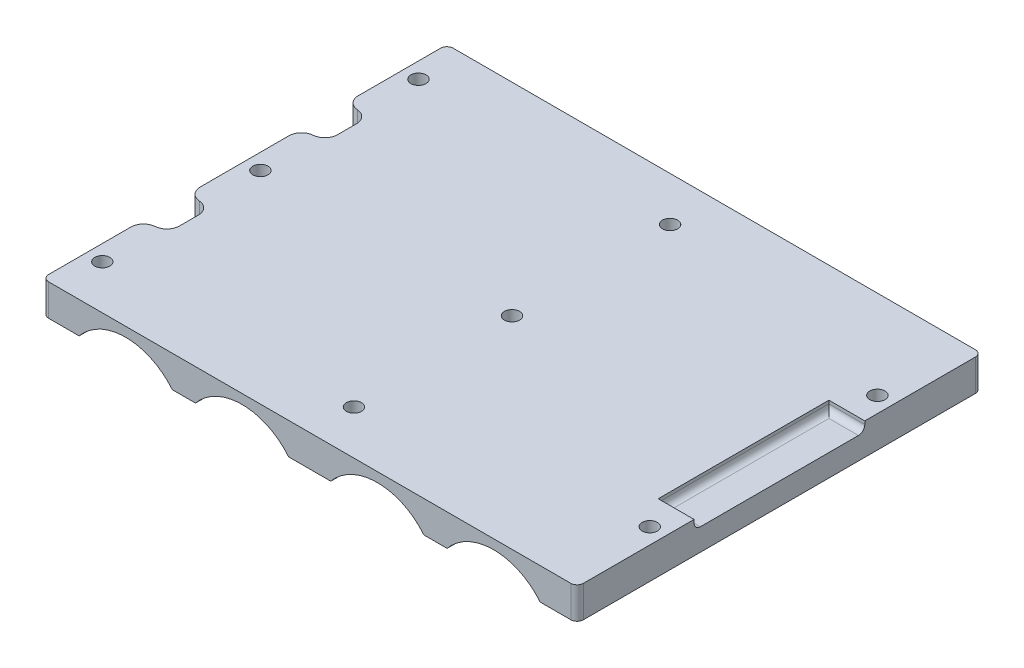
SolidWorks part; units mm, degrees
ref_plane "Front Plane" through (0, 0, 0) normal (0, 0, 1) x (1, 0, 0)
ref_plane "Top Plane" through (0, 0, 0) normal (0, 1, 0) x (1, 0, 0)
ref_plane "Right Plane" through (0, 0, 0) normal (1, 0, 0) x (0, 0, -1)
sketch "Sketch2" plane through (0, 0, 0) normal (0, 0, 1) x (1, 0, 0)
  line L2 (3.3345, -5) -> (-3.3345, -5)
  line L3 (-18.0655, -5) -> (-21.7345, -5)
  line L4 (-36.4655, -5) -> (-42.3, -5)
  line L5 (-42.3, -5) -> (-42.3, 0)
  line L7 (36.4655, -5) -> (42.3, -5)
  line L9 (18.0655, -5) -> (21.7345, -5)
  line L11 (42.3, -5) -> (42.3, 0)
  line L12 (-42.3, 0) -> (42.3, 0)
  line L13 (0, -55) -> (0, 55) construction
  line L14 (25.85, 0) -> (-25.85, 0) construction
  arc A0 (-3.3345, -5) -> (-18.0655, -5) centre (-10.7, -11) ccw
  arc A1 (-21.7345, -5) -> (-36.4655, -5) centre (-29.1, -11) ccw
  arc A2 (21.7345, -5) -> (36.4655, -5) centre (29.1, -11) cw
  arc A3 (3.3345, -5) -> (18.0655, -5) centre (10.7, -11) cw
  point P3 (0, 0)
  dimension "D1" = 9.5
  dimension "D2" = 13.2
  dimension "D3" = 11
  dimension "D4" = 18.4
  dimension "D5" = 18.4
  dimension "D6" = 5
  dimension "D7" = 21.4
extrude "Boss-Extrude1" add sketch "Sketch2" along normal mid plane 64 contours A0 L3 A1 L4 L5 L12 L11 L7 A2 L9 A3 L2
hole_wizard "M2 Clearance Hole1" positions "Sketch7" profile "Sketch8" hole size "M2" standard "ANSI Metric" end condition through all
sketch "Sketch7" plane through (0, -5, 0) normal (0, -1, 0) x (-1, 0, 0)
  line L2 (39.8, 25) -> (0, 25) construction
  line L3 (39.8, 25) -> (39.8, -25) construction
  line L4 (39.8, -25) -> (0, -25) construction
  line L5 (0, 25) -> (0, -25) construction
  line L10 (42.3, -32) -> (42.3, 32) construction
  line L12 (-42.3, -32) -> (-42.3, 32) construction
  line L13 (-36.4655, 32) -> (-42.3, 32) construction
  line L14 (-36.4655, -32) -> (-42.3, -32) construction
  line L15 (0, 55) -> (0, -55) construction
  point P0 (0, 25)
  point P2 (0, 0)
  point P4 (0, -25)
  point P6 (39.8, -25)
  point P8 (39.8, 0)
  point P10 (39.8, 25)
  point P291 (-39.8, -18)
  point P296 (-39.8, 18)
  dimension "D1" = 2.5
  dimension "D3" = 50
  dimension "D5" = 50
  dimension "D6" = 2.5
  dimension "D7" = 2.5
  dimension "D8" = 14
  dimension "D9" = 14
sketch "Sketch8" plane through (0, -5, -25) normal (1, 0, 0) x (0, 0, -1)
  line L0 (0, 0) -> (0, 5)
  line L1 (0, 5) -> (1.2, 5)
  line L2 (1.2, 5) -> (1.2, 0)
  line L5 (1.2, 0) -> (0, 0)
  line L11 (0, -6.35) -> (0, 107.95) construction
  dimension "Thru Hole Dia." = 2.4
  dimension "Thru Hole Depth" = 5
fillet "Fillet1" radius 1 4 edges at (-42.3, -2.5, -32) (42.3, -2.5, -32) (-42.3, -2.5, 32) (42.3, -2.5, 32)
sketch "Sketch9" plane through (0, 0, 0) normal (0, 1, 0) x (1, 0, 0)
  line L0 (42.3, -31) -> (42.3, 31) construction
  line L1 (42.3, -13.5) -> (36.63, -13.5)
  line L2 (42.3, -13.5) -> (42.3, 13.5)
  line L3 (42.3, 13.5) -> (36.63, 13.5)
  line L4 (36.63, -13.5) -> (36.63, 13.5)
  point P6 (42.3, 0)
  point P7 (42.3, 0)
  dimension "D1" = 5.67
  dimension "D2" = 27
extrude "Cut-Extrude1" cut sketch "Sketch9" against normal blind 1.5
fillet "Fillet2" radius 1 3 edges at (39.465, -1.5, -13.5) (36.63, -1.5, 0) (39.465, -1.5, 13.5)
sketch "Sketch11" plane through (0, -5, 0) normal (0, -1, 0) x (1, 0, 0)
  line L0 (2.75, 0) -> (-2.75, 0) construction
  line L1 (-32.3, 19) -> (-42.3, 19)
  line L2 (-32.3, 19) -> (-32.3, 6)
  line L3 (-32.3, 6) -> (-42.3, 6)
  line L4 (-42.3, 19) -> (-42.3, 6)
  line L5 (-32.3, 19) -> (-42.3, 6) construction
  line L6 (-32.3, 6) -> (-42.3, 19) construction
  line L7 (-32.3, -6) -> (-42.3, -6)
  line L8 (-32.3, -6) -> (-32.3, -19)
  line L9 (-32.3, -19) -> (-42.3, -19)
  line L10 (-42.3, -6) -> (-42.3, -19)
  line L11 (-32.3, -6) -> (-42.3, -19) construction
  line L12 (-32.3, -19) -> (-42.3, -6) construction
  line L13 (-42.3, 31) -> (-42.3, -31) construction
  point P0 (-37.3, 12.5)
  point P5 (-37.3, -12.5)
  dimension "D1" = 12.5
  dimension "D2" = 12.5
  dimension "D3" = 13
  dimension "D4" = 13
  dimension "D5" = 10
extrude "Cut-Extrude3" cut sketch "Sketch11" against normal blind 1.5
sketch "Sketch12" plane through (0, -3.5, 0) normal (0, -1, 0) x (1, 0, 0)
  line L0 (-21.7345, 32) -> (-36.4655, 32) construction
  line L4 (-42.3, 16) -> (-42.3, 9)
  line L5 (2.75, 0) -> (-2.75, 0) construction
  line L8 (-40.6, 16) -> (-42.3, 16)
  line L11 (-42.3, 9) -> (-40.6, 9)
  line L12 (-40.6, -9) -> (-42.3, -9)
  line L13 (-42.3, -6) -> (-42.3, -19) construction
  line L14 (-42.3, -9) -> (-42.3, -16)
  line L15 (-42.3, -16) -> (-40.6, -16)
  line L16 (-38.6, 14) -> (-38.6, 11)
  line L17 (-38.6, -11) -> (-38.6, -14)
  line L18 (-42.3, 19) -> (-42.3, 6) construction
  arc A4 (-40.6, 16) -> (-38.6, 14) centre (-40.6, 14) cw
  arc A5 (-38.6, 11) -> (-40.6, 9) centre (-40.6, 11) cw
  arc A6 (-40.6, -9) -> (-38.6, -11) centre (-40.6, -11) cw
  arc A7 (-38.6, -14) -> (-40.6, -16) centre (-40.6, -14) cw
  point P3 (-29.1, 32)
  point P4 (-41.45, 16)
  dimension "D5" = 9
  dimension "D6" = 2
  dimension "D7" = 2
  dimension "D1" = 9.5
  dimension "D2" = 7
  dimension "D3" = 7
  dimension "D4" = 18
extrude "Cut-Extrude4" cut sketch "Sketch12" against normal through all
fillet "Fillet4" radius 2 4 edges at (-42.3, -1.75, -16) (-42.3, -1.75, -9) (-42.3, -1.75, 9) (-42.3, -1.75, 16)
